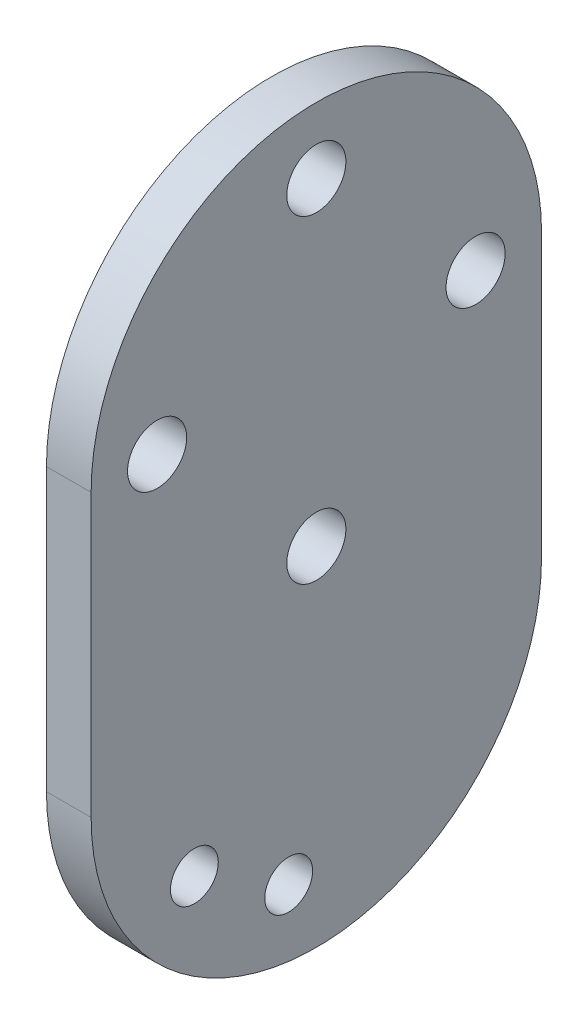
SolidWorks part; units mm, degrees
ref_plane "Front" through (0, 0, 0) normal (0, 0, 1) x (1, 0, 0)
ref_plane "Top" through (0, 0, 0) normal (0, 1, 0) x (1, 0, 0)
ref_plane "Right" through (0, 0, 0) normal (1, 0, 0) x (0, 0, -1)
sketch "Sketch2" plane through (0, 0, 0) normal (1, 0, 0) x (0, 0, -1)
  line L0 (0, -5) -> (0, 5) construction
  line L1 (-16, -5) -> (-16, 5)
  line L2 (16, -5) -> (16, 5)
  line L3 (0, -6.3137) -> (7.4244, -19.1732)
  line L4 (41.4915, -10.0987) -> (41.4915, 9.9013) construction
  line L7 (25.4915, -10.0987) -> (25.4915, 9.9013)
  line L8 (0, -6.3137) -> (-15.946, -6.3137)
  line L9 (0, -6.3137) -> (-7.9856, -13.0144)
  line L10 (-7.9856, -13.0144) -> (0, -6.3137)
  line L11 (-1.7395, -16.1792) -> (0, -6.3137)
  line L12 (57.4915, -10.0987) -> (57.4915, 9.9013)
  line L13 (41.4915, -10.0987) -> (25.4915, -10.0987)
  line L14 (41.4915, -10.0987) -> (38.7131, -25.8556)
  line L15 (38.7131, -25.8556) -> (41.4915, -10.0987)
  line L16 (41.4915, -10.0987) -> (29.2348, -20.3833)
  arc A0 (-16, -5) -> (16, -5) centre (0, -5) ccw
  arc A1 (16, 5) -> (-16, 5) centre (0, 5) ccw
  circle A2 centre (0, 5) radius 11.3137
  circle A3 centre (0, 16.3137) radius 2.1
  circle A4 centre (0, -6.3137) radius 2.1
  circle A5 centre (11.3137, 5) radius 2.1
  circle A6 centre (-11.3137, 5) radius 2.1
  circle A7 centre (0, -5) radius 11.3137
  circle A18 centre (-7.9856, -13.0144) radius 1.7
  circle A19 centre (-1.7395, -16.1792) radius 1.7
  arc A20 (25.4915, -10.0987) -> (57.4915, -10.0987) centre (41.4915, -10.0987) ccw
  arc A21 (57.4915, 9.9013) -> (25.4915, 9.9013) centre (41.4915, 9.9013) ccw
  circle A22 centre (41.4915, 9.9013) radius 11.3137
  circle A23 centre (41.4915, -10.0987) radius 11.3137
  circle A24 centre (39.5269, -21.2405) radius 1.7
  circle A25 centre (32.8247, -17.371) radius 1.7
  circle A26 centre (41.4915, 21.215) radius 2.1
  circle A27 centre (30.1778, 9.9013) radius 2.1
  circle A28 centre (41.4915, -1.4124) radius 2.1
  circle A29 centre (52.8052, 9.9013) radius 2.1
  point P2 (0, 0)
  point P24 (41.4915, -0.0987)
  dimension "D1" = 16
  dimension "D2" = 22.6274
  dimension "D3" = 22.6274
  dimension "D4" = 40
  dimension "D6" = 120
  dimension "D7" = 80
  dimension "D5" = 40
  dimension "D8" = 40
extrude "Boss-Extrude1" add sketch "Sketch2" along normal blind 3.175 contours A28 A22 A23 L13 L14 A24 | A28 A22 A23 | A29 A22 A26 A27 A23 | A29 A22 A23 A24 L14 A20 L12 A21 L7 L13 A27 A26 | A25 A23 L13 A20 L16 | A25 L16 A20 L14 A24 A23 | A25 A23 A24 L14 L16 | A25 L16 L13 A23 region at (0, -0.0987, -26.1021) region at (0, -14.5801, -28.6268) region at (0, -9.4732, -43.1707) region at (0, -12.4335, -34.6299) region at (0, -22.0009, -34.6197) region at (0, -16.2359, -37.9482) region at (0, 1.1064, -41.4915) region at (0, 10.2275, -41.4915)
